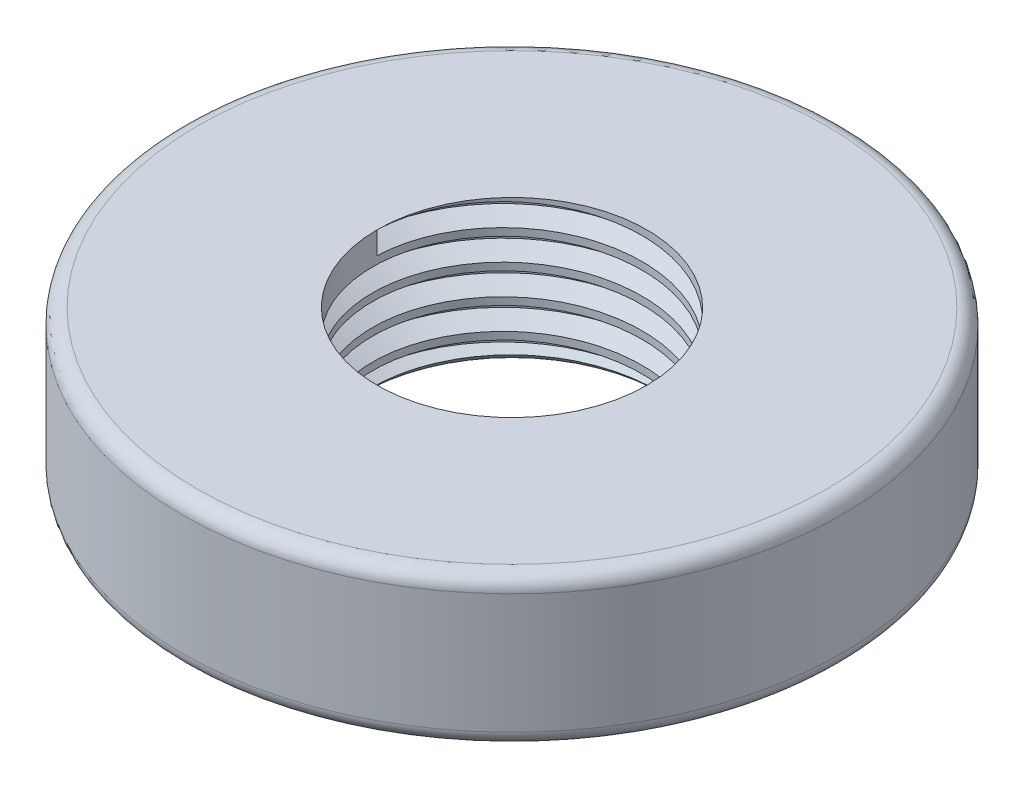
SolidWorks part; units mm, degrees
material "AISI 1020"
ref_plane "Plano superior" through (0, 0, 0) normal (0, 0, 1) x (1, 0, 0)
ref_plane "Plano frontal" through (0, 0, 0) normal (0, 1, 0) x (1, 0, 0)
ref_plane "Plano direito" through (0, 0, 0) normal (1, 0, 0) x (0, 0, -1)
sketch "Esboço1" plane through (0, 0, 0) normal (0, 1, 0) x (1, 0, 0)
  circle A0 centre (0, 0) radius 11
  dimension "D1" = 22
extrude "Ressalto-extrusão1" add sketch "Esboço1" along normal blind 5
fillet "Filete1" radius 0.5 2 edges at (0, 5, 11) (0, 0, 11)
hole_wizard "Furo roscado de M10x1.01" positions "Esboço3" profile "Esboço4" tap size "M10x1.0" standard "DIN" end condition up to next
sketch "Esboço3" plane through (0, 0, 0) normal (0, -1, 0) x (-1, 0, 0)
  point P0 (0, 0)
sketch "Esboço4" plane through (0, 0, 0) normal (1, 0, 0) x (0, 0, -1)
  line L0 (0, 0) -> (0, 5)
  line L1 (0, 5) -> (4.5, 5)
  line L2 (4.5, 5) -> (4.5, 0.525)
  line L3 (4.5, 0.525) -> (5.025, 0)
  line L5 (5.025, 0) -> (0, 0)
  line L6 (-4.5, 0.525) -> (-5.025, 0) construction
  line L11 (0, -6.35) -> (0, 107.95) construction
  dimension "Thru Tap Drill Dia." = 9
  dimension "Thru Tap Drill Depth" = 5
  dimension "Near C'Sink Dia." = 10.05
  dimension "Near C'Sink Angle" = 90
cosmetic thread "Rosca de furo1"
thread "Rosca1" pitch 1 method cut profile "Perfil da rosca1" start angle 0, offset 0, length 0, pitch 1, diameter 9
ref_plane "Plano1" through (-4.5, 5, 0) normal (0, 0, 1) x (-1, 0, 0)
sketch "Perfil da rosca1" plane through (-4.5, 5, 0) normal (0, 0, 1) x (-1, 0, 0)
  line L0 (0, 0) -> (0, 1) construction
  line L1 (0, 0) -> (0.5413, 0.3125)
  line L2 (0.5413, 0.3125) -> (0.5413, 0.4375)
  line L3 (0.5413, 0.4375) -> (0, 0.75)
  line L4 (0.5413, 0.375) -> (0, 0.375) construction
  line L11 (0, 0) -> (0, 0.75)
  point P2 (0, 0)
  dimension "Pitch" = 1
  dimension "Profile_Angle" = 60
  dimension "Profile_Land" = 0.125
  dimension "Profile_Height" = 0.5413
